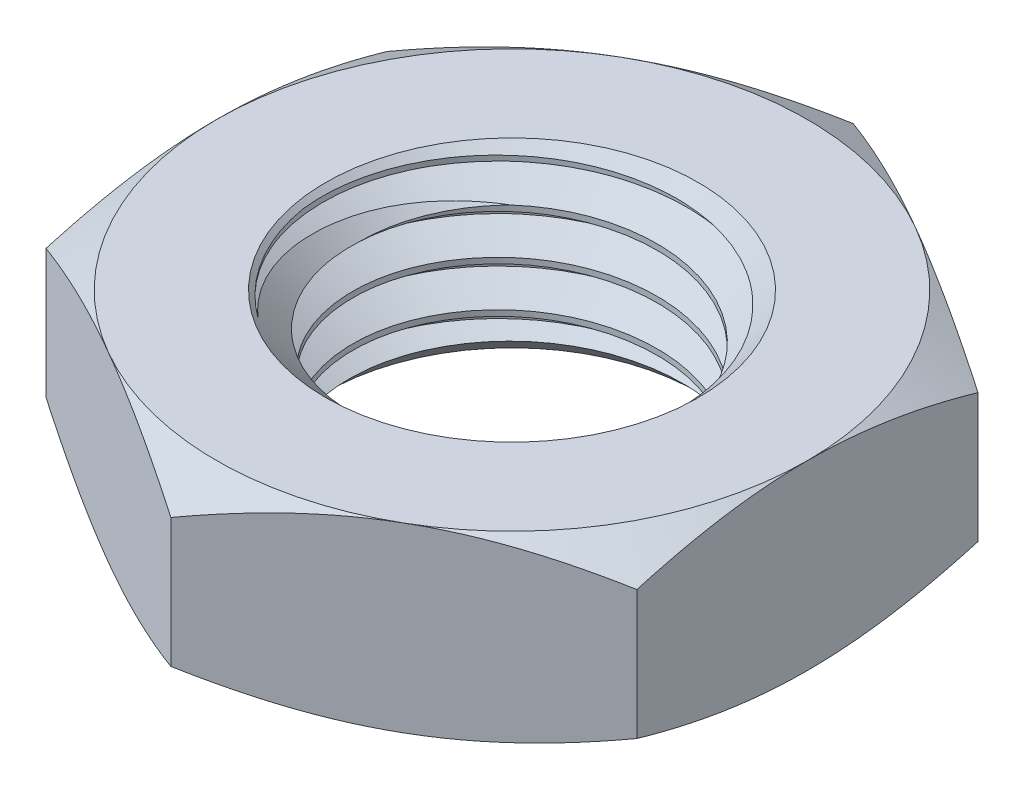
SolidWorks part; units mm, degrees
ref_plane "Front Plane" through (0, 0, 0) normal (0, 0, 1) x (1, 0, 0)
ref_plane "Top Plane" through (0, 0, 0) normal (0, 1, 0) x (1, 0, 0)
ref_plane "Right Plane" through (0, 0, 0) normal (1, 0, 0) x (0, 0, -1)
sketch "Sketch0" plane through (0, 0, 0) normal (0, 1, 0) x (1, 0, 0)
  line L0 (0, 0) -> (0, 4) construction
  line L1 (-6.5, 3.7528) -> (-6.5, -3.7528)
  line L2 (-6.5, -3.7528) -> (0, -7.5056)
  line L3 (0, -7.5056) -> (6.5, -3.7528)
  line L4 (6.5, -3.7528) -> (6.5, 3.7528)
  line L5 (6.5, 3.7528) -> (0, 7.5056)
  line L6 (0, 7.5056) -> (-6.5, 3.7528)
  line L7 (0, 0) -> (0, -4) construction
  line L8 (0, 0) -> (2.8284, -2.8284) construction
  circle A0 centre (0, 0) radius 6.5 construction
  circle A1 centre (0, 0) radius 4
  point P12 (0, 4)
  point P14 (0, -4)
  point P15 (-6.5, 3.7528)
  point P16 (6.5, 3.7528)
  point P17 (0, -4)
  point P19 (2.8284, -2.8284)
  dimension "Thread Size" = 8
  dimension "D1" = 45
  dimension "Hex" = 13
extrude "Boss-Extrude1" add sketch "Sketch0" along normal mid plane 4
sketch "Sketch1" plane through (0, 0, 0) normal (1, 0, 0) x (0, 0, -1)
  line L0 (4, -2) -> (4, 2) construction
  line L1 (-3.7528, -2) -> (-7.5056, -2) construction
  line L2 (4, -2) -> (4, 2) construction
  line L3 (-7.5056, 2) -> (-7.5056, -2) construction
  line L4 (-4.1083, -1.9375) -> (-4.1083, -2.9375) construction
  line L5 (-4.1083, -2.9375) -> (-3.2422, -2.4375) construction
  line L6 (-3.2422, -2.4375) -> (-4.1083, -1.9375) construction
  line L7 (-3.2422, -2.4375) -> (-3.3505, -2.4375) construction
  line L8 (-4, -2) -> (-4, -2.875) construction
  line L9 (-3.3505, -2.375) -> (-3.3505, -2.5) construction
  line L10 (-4, -2.4375) -> (-4.1083, -2.4375) construction
  line L11 (-4.0541, -1.9687) -> (-4.0541, -2.9062) construction
  line L12 (-7.5056, 2) -> (-7.5056, -2)
  line L13 (7.5056, 2) -> (7.5056, -2) construction
  line L14 (7.5056, 2) -> (7.5056, -2)
  point P14 (-4.0541, -2.4375)
  point P17 (-4.0541, -2.4375)
  dimension "D1" = 60
  dimension "Pitch" = 1
  dimension "D3" = 0.125
sketch "Sketch5" plane through (0, 2, 0) normal (0, 1, 0) x (1, 0, 0)
  circle A0 centre (0, 0) radius 6.5 construction
  circle A1 centre (0, 0) radius 6.5
extrude "Cut-Extrude2" cut sketch "Sketch5" against normal through all draft 60 flip side to cut
mirror "Mirror2" about plane through (0, 0, 0) normal (0, 1, 0) of "Cut-Extrude2"
sketch "Sketch2" plane through (0, 2, 0) normal (0, 1, 0) x (1, 0, 0)
  circle A0 centre (0, 0) radius 4 construction
  circle A1 centre (0, 0) radius 4
sketch "Sketch6" plane through (0, 0, 0) normal (1, 0, 0) x (0, 0, -1)
  line L0 (-4.0541, -1.9687) -> (-4.0541, -2.9062)
  line L1 (-4.0541, -2.9062) -> (-3.3505, -2.5)
  line L2 (-3.3505, -2.5) -> (-3.3505, -2.375)
  line L3 (-3.3505, -2.375) -> (-4.0541, -1.9687)
sketch "Sketch7" plane through (0, 2, 0) normal (0, 1, 0) x (1, 0, 0)
  circle A2 centre (0, 0) radius 4.1
  circle A3 centre (0, 0) radius 4.1
  dimension "D1" = 0.1
ref_plane "Plane1" through (0, 5, 0) normal (0, 1, 0) x (1, 0, 0)
sketch "Sketch8" plane through (0, 5, 0) normal (0, 1, 0) x (1, 0, 0)
  circle A0 centre (0, 0) radius 4 construction
  circle A1 centre (0, 0) radius 4
curve "Helix/Spiral1" pitch 1 height 6 turns 6
sweep "Sweep1" add profiles "Sketch6" path "Helix/Spiral1"
sketch "Sketch9" plane through (0, -2, 0) normal (0, -1, 0) x (1, 0, 0)
  circle A0 centre (0, 0) radius 4 construction
  circle A1 centre (0, 0) radius 4 construction
  circle A2 centre (0, 0) radius 4.1
  dimension "D1" = 0.1
extrude "Cut-Extrude3" cut sketch "Sketch9" against normal through all draft 45 and the other way through all draft 45
mirror "Mirror3" about plane through (0, 0, 0) normal (0, 1, 0) of "Cut-Extrude3"
equation "\"D3@Helix/Spiral1\"=\"Height@Boss-Extrude1\"+(2*\"Pitch@Sketch1\")"
equation "\"D3@Sketch1\" = \"Pitch@Sketch1\" / 8"
equation "\"D4@Helix/Spiral1\"=\"Pitch@Sketch1\""
